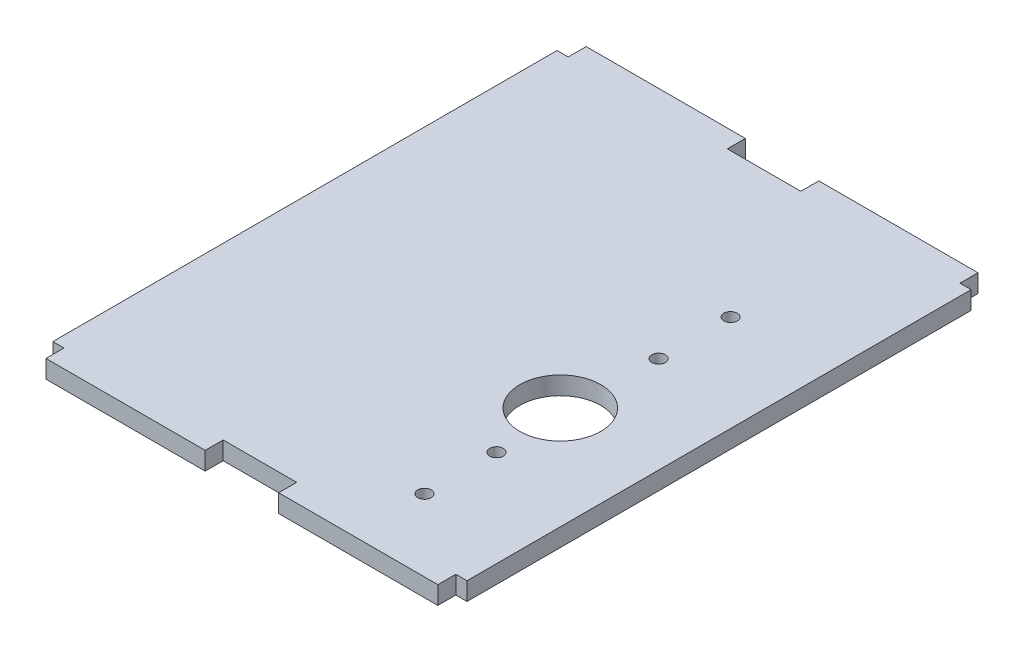
SolidWorks part; units mm, degrees
ref_plane "Front Plane" through (0, 0, 0) normal (0, 0, 1) x (1, 0, 0)
ref_plane "Top Plane" through (0, 0, 0) normal (0, 1, 0) x (1, 0, 0)
ref_plane "Right Plane" through (0, 0, 0) normal (1, 0, 0) x (0, 0, -1)
sketch "Sketch1" plane through (0, 0, 0) normal (0, 1, 0) x (1, 0, 0)
  line L1 (0, 0) -> (292.1, 0)
  line L2 (0, 0) -> (0, 355.6)
  line L3 (0, 355.6) -> (292.1, 355.6)
  line L4 (292.1, 0) -> (292.1, 355.6)
  ellipse E1 centre (219.5122, 138.3861) end of major axis (248.0872, 138.3861) minor radius 28.574
  dimension "D1" = 355.6
  dimension "D2" = 292.1
extrude "Boss-Extrude1" add sketch "Sketch1" along normal blind 12.7
sketch "Sketch2" plane through (0, 0, 0) normal (0, -1, 0) x (1, 0, 0)
  line L0 (0, 0) -> (292.1, 0) construction
  line L1 (0, -355.6) -> (0, 0) construction
  circle A0 centre (224.028, -38.1) radius 4.7625
  circle A1 centre (224.028, -88.9) radius 4.7625
  circle A2 centre (224.028, -203.2) radius 4.7625
  circle A3 centre (224.028, -254) radius 4.7625
  dimension "D3" = 88.9
  dimension "D6" = 9.525
  dimension "D1" = 38.1
  dimension "D2" = 224.028
  dimension "D4" = 203.2
  dimension "D5" = 254
  dimension "D7" = 224.028
  dimension "D8" = 224.028
  dimension "D9" = 224.028
extrude "Cut-Extrude1" cut sketch "Sketch2" against normal blind 12.7
sketch "Sketch3" plane through (0, 12.7, 0) normal (0, 1, 0) x (1, 0, 0)
  line L0 (146.05, 355.6) -> (146.05, 250.206) construction
  line L1 (0, 177.8) -> (22.2548, 177.8) construction
  line L2 (7.874, 355.6) -> (120.142, 355.6)
  line L3 (7.874, 355.6) -> (7.874, 368.3)
  line L4 (0, 355.6) -> (0, 0)
  line L5 (0, 0) -> (292.1, 0)
  line L6 (292.1, 0) -> (292.1, 355.6)
  line L7 (292.1, 355.6) -> (0, 355.6)
  line L8 (0, 355.6) -> (0, 0) construction
  line L9 (0, 0) -> (292.1, 0) construction
  line L10 (292.1, 0) -> (292.1, 355.6) construction
  line L11 (292.1, 355.6) -> (0, 355.6) construction
  line L12 (7.874, 368.3) -> (120.142, 368.3)
  line L13 (120.142, 355.6) -> (120.142, 368.3)
  line L14 (284.226, 368.3) -> (171.958, 368.3)
  line L15 (171.958, 355.6) -> (171.958, 368.3)
  line L16 (284.226, 355.6) -> (171.958, 355.6)
  line L17 (284.226, 355.6) -> (284.226, 368.3)
  line L18 (284.226, 0) -> (284.226, -12.7)
  line L19 (284.226, 0) -> (171.958, 0)
  line L20 (171.958, 0) -> (171.958, -12.7)
  line L21 (284.226, -12.7) -> (171.958, -12.7)
  line L22 (7.874, -12.7) -> (120.142, -12.7)
  line L23 (120.142, 0) -> (120.142, -12.7)
  line L24 (7.874, 0) -> (120.142, 0)
  line L25 (7.874, 0) -> (7.874, -12.7)
  dimension "D2" = 25.908
  dimension "D3" = 112.268
  dimension "D4" = 12.7
  dimension "D1" = 0
extrude "Boss-Extrude2" add sketch "Sketch3" against normal blind 12.7
sketch "Sketch4" plane through (0, 0, 0) normal (0, -1, 0) x (1, 0, 0)
  line L20 (0, 0) -> (0, -355.6)
  line L21 (0, -355.6) -> (7.874, -355.6)
  line L22 (7.874, -355.6) -> (7.874, -368.3)
  line L23 (7.874, -368.3) -> (120.142, -368.3)
  line L24 (120.142, -368.3) -> (120.142, -355.6)
  line L25 (120.142, -355.6) -> (171.958, -355.6)
  line L26 (171.958, -355.6) -> (171.958, -368.3)
  line L27 (171.958, -368.3) -> (284.226, -368.3)
  line L28 (284.226, -368.3) -> (284.226, -355.6)
  line L29 (284.226, -355.6) -> (292.1, -355.6)
  line L30 (292.1, -355.6) -> (292.1, 0)
  line L31 (292.1, 0) -> (284.226, 0)
  line L32 (284.226, 0) -> (284.226, 12.7)
  line L33 (284.226, 12.7) -> (171.958, 12.7)
  line L34 (171.958, 12.7) -> (171.958, 0)
  line L35 (171.958, 0) -> (120.142, 0)
  line L36 (120.142, 0) -> (120.142, 12.7)
  line L37 (120.142, 12.7) -> (7.874, 12.7)
  line L38 (7.874, 12.7) -> (7.874, 0)
  line L39 (7.874, 0) -> (0, 0)
  line L40 (0, 0) -> (0, -355.6)
  line L41 (0, -355.6) -> (7.874, -355.6)
  line L42 (7.874, -355.6) -> (7.874, -368.3)
  line L43 (7.874, -368.3) -> (120.142, -368.3)
  line L44 (120.142, -368.3) -> (120.142, -355.6)
  line L45 (120.142, -355.6) -> (171.958, -355.6)
  line L46 (171.958, -355.6) -> (171.958, -368.3)
  line L47 (171.958, -368.3) -> (284.226, -368.3)
  line L48 (284.226, -368.3) -> (284.226, -355.6)
  line L49 (284.226, -355.6) -> (292.1, -355.6)
  line L50 (292.1, -355.6) -> (292.1, 0)
  line L51 (292.1, 0) -> (284.226, 0)
  line L52 (284.226, 0) -> (284.226, 12.7)
  line L53 (284.226, 12.7) -> (171.958, 12.7)
  line L54 (171.958, 12.7) -> (171.958, 0)
  line L55 (171.958, 0) -> (120.142, 0)
  line L56 (120.142, 0) -> (120.142, 12.7)
  line L57 (120.142, 12.7) -> (7.874, 12.7)
  line L58 (7.874, 12.7) -> (7.874, 0)
  line L59 (7.874, 0) -> (0, 0)
  circle A5 centre (224.028, -203.2) radius 4.7625 construction
  circle A6 centre (224.028, -88.9) radius 4.7625 construction
  dimension "D3" = 109.5375
  dimension "D1" = 0
